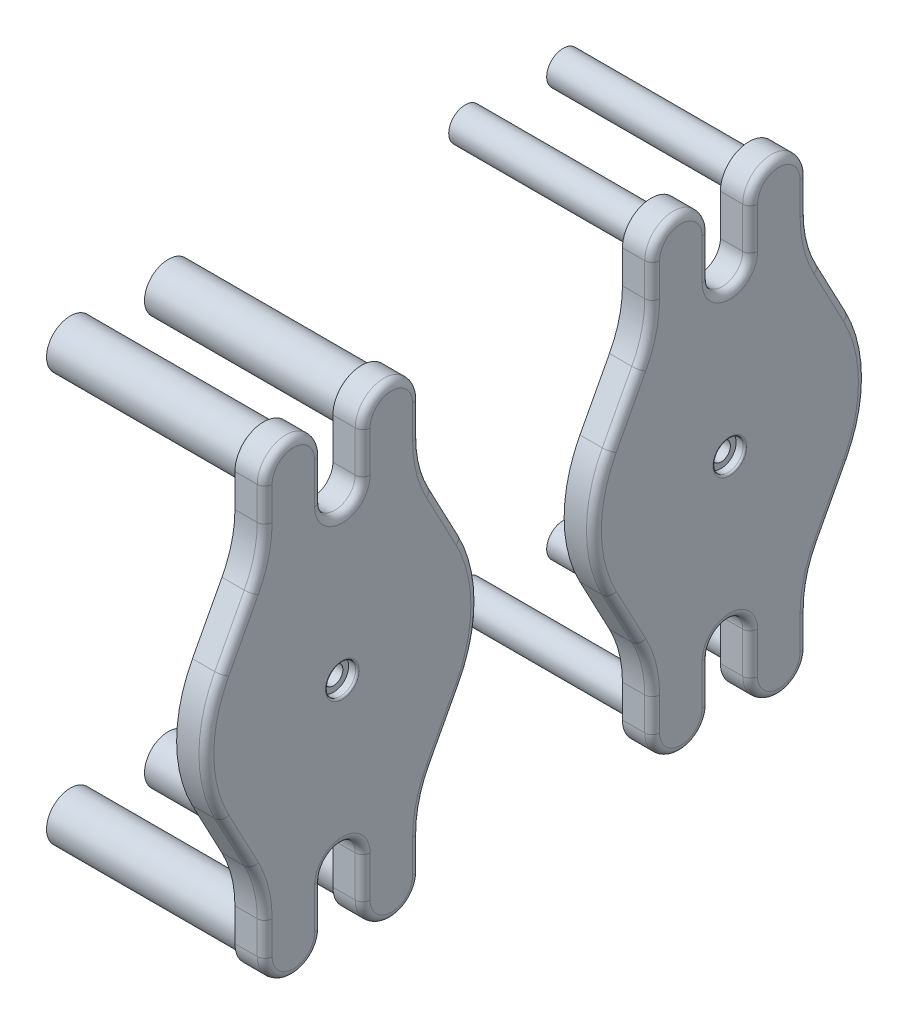
SolidWorks part; units mm, degrees
note: The reader was unsure of these and kept them because the rebuilt part matched: shared geometry of "Sketch12<6>", "Sketch13<3>".
other "Markup1"
sketch "Sketch9" plane through (-25.745, 62.7203, -36.576) normal (-0.5706, 0.1284, -0.8112) x (-0.8147, 0.0363, 0.5788)
ref_plane "Front Plane" through (0, 0, 0) normal (0, 0, 1) x (1, 0, 0)
ref_plane "Top Plane" through (0, 0, 0) normal (0, 1, 0) x (1, 0, 0)
ref_plane "Right Plane" through (0, 0, 0) normal (1, 0, 0) x (0, 0, -1)
sketch "Sketch1" plane through (0, 0, 0) normal (0, 0, 1) x (1, 0, 0)
  line L0 (8.255, 0) -> (-8.255, 0) construction
  line L1 (20.255, 0) -> (-20.255, 0) construction
  line L2 (8.255, 0) -> (8.255, 18.25)
  line L3 (8.255, 18.25) -> (20.255, 18.25)
  line L4 (20.255, 18.25) -> (20.255, 0)
  line L5 (8.255, 0) -> (20.255, 0)
  point P4 (0, 0)
  point P8 (0, 0)
  dimension "D1" = 16.51
  dimension "D2" = 12
  dimension "D3" = 18.25
revolve "Revolve1" add sketch "Sketch1" angle 360 about L5
sketch "Sketch2" plane through (8.255, 0, 0) normal (-1, 0, 0) x (0, 0, 1)
  circle A0 centre (0, 0) radius 3.7145
  dimension "D1" = 7.429
extrude "Cut-Extrude1" cut sketch "Sketch2" against normal blind 8.5725
sketch "Sketch3" plane through (20.255, 0, 0) normal (1, 0, 0) x (0, 0, -1)
  line L0 (-20.8953, -55) -> (-20.8953, -46.1532)
  line L1 (13.175, -55) -> (-13.175, -55) construction
  line L2 (13.175, -55) -> (13.175, 55) construction
  line L3 (13.175, 55) -> (-13.175, 55) construction
  line L4 (-13.175, -55) -> (-13.175, 55) construction
  line L5 (13.175, -55) -> (-13.175, 55) construction
  line L6 (13.175, 55) -> (-13.175, -55) construction
  line L7 (-24.3823, -32.1152) -> (-32.3245, -17.1152)
  line L9 (-5.4548, -55) -> (-5.4548, -44)
  line L11 (5.4547, -44) -> (5.4547, -55)
  line L12 (20.8953, -55) -> (20.8953, -46.1532)
  line L13 (24.3823, -32.1152) -> (32.3245, -17.1152)
  line L14 (55, 0) -> (-55, 0) construction
  line L15 (13.175, -55) -> (-13.175, 55) construction
  line L16 (13.175, 55) -> (-13.175, -55) construction
  line L17 (13.175, 55) -> (-13.175, 55) construction
  line L18 (24.3823, 32.1152) -> (32.3245, 17.1152)
  line L19 (20.8953, 55) -> (20.8953, 46.1532)
  line L20 (5.4547, 44) -> (5.4547, 55)
  line L21 (-5.4548, 55) -> (-5.4548, 44)
  line L22 (-24.3823, 32.1152) -> (-32.3245, 17.1152)
  line L23 (-20.8953, 55) -> (-20.8953, 46.1532)
  arc A15 (32.3245, -17.1152) -> (32.3245, 17.1152) centre (0, 0) ccw
  arc A16 (-5.4548, 55) -> (-20.8953, 55) centre (-13.175, 55) ccw
  arc A17 (-20.8953, -55) -> (-5.4548, -55) centre (-13.175, -55) ccw
  arc A18 (5.4547, -55) -> (20.8953, -55) centre (13.175, -55) ccw
  arc A19 (20.8953, 55) -> (5.4547, 55) centre (13.175, 55) ccw
  arc A20 (-5.4548, -44) -> (5.4547, -44) centre (0, -44) cw
  arc A21 (20.8953, -46.1532) -> (24.3823, -32.1152) centre (50.8953, -46.1532) cw
  arc A22 (-20.8953, -46.1532) -> (-24.3823, -32.1152) centre (-50.8953, -46.1532) ccw
  arc A23 (-20.8953, 46.1532) -> (-24.3823, 32.1152) centre (-50.8953, 46.1532) cw
  arc A24 (20.8953, 46.1532) -> (24.3823, 32.1152) centre (50.8953, 46.1532) ccw
  arc A25 (-5.4548, 44) -> (5.4547, 44) centre (0, 44) ccw
  arc A26 (5.4547, 55) -> (20.8953, 55) centre (13.175, 55) cw
  arc A27 (-20.8953, 55) -> (-5.4548, 55) centre (-13.175, 55) cw
  arc A29 (-32.3245, 17.1152) -> (-32.3245, -17.1152) centre (0, 0) ccw
  circle M2 centre (0, 0) radius 18.25
  dimension "D3" = 15.4405
  dimension "D5" = 7.7203
  dimension "D4" = 30
  dimension "D7" = 15
  dimension "D9" = 110
  dimension "D1" = 73.152
  dimension "D6" = 15
  dimension "D2" = 26.35
  dimension "D8" = 11
extrude "Boss-Extrude1" add sketch "Sketch3" along normal blind 8 separate body contours L22 A29 L7 A22 L0 A17 L9 A20 L11 A18 L12 A21 L13 A15 L18 A24 L19 A19 L20 A25 L21 A16 L23 A23 M2 | M2
sketch "Sketch4" plane through (20.255, 0, 0) normal (-1, 0, 0) x (0, 0, 1)
  line L0 (-20.8953, 55) -> (-5.4547, 55) construction
  line L1 (13.175, -55) -> (-13.175, -55) construction
  line L2 (13.175, -55) -> (13.175, 55) construction
  line L3 (13.175, 55) -> (-13.175, 55) construction
  line L4 (-13.175, -55) -> (-13.175, 55) construction
  line L5 (13.175, -55) -> (-13.175, 55) construction
  line L6 (13.175, 55) -> (-13.175, -55) construction
  circle A0 centre (-13.175, 55) radius 4.75
  circle A1 centre (13.175, -55) radius 4.75
  circle A2 centre (13.175, 55) radius 4.75
  circle A3 centre (-13.175, -55) radius 4.75
  arc A4 (-5.4547, 55) -> (-20.8953, 55) centre (-13.175, 55) ccw construction
  circle A5 centre (-13.175, 55) radius 6.4
  circle A6 centre (13.175, 55) radius 6.4
  circle A7 centre (13.175, -55) radius 6.4
  circle A8 centre (-13.175, -55) radius 6.4
  point P6 (0, 0)
  dimension "D1" = 9.5
  dimension "D2" = 12.8
extrude "Boss-Extrude2" add sketch "Sketch4" along normal blind 52
sketch "Sketch5" plane through (8.255, 0, 0) normal (-1, 0, 0) x (0, 0, 1)
  circle A0 centre (0, 0) radius 18.25
  dimension "D1" = 36.5
fillet "Fillet1" radius 2 24 edges at (28.255, 38.9209, 21.7801) (28.255, 50.5766, 20.8953) (28.255, 62.7203, 13.175) (28.255, 49.5, 5.4548) (28.255, 38.5453, 0) (28.255, 49.5, -5.4547) (28.255, 62.7203, -13.175) (28.255, 50.5766, -20.8953) (28.255, 38.9209, -21.7801) (28.255, 24.6152, -28.3534) (28.255, 0, -36.576) (28.255, -24.6152, -28.3534) (28.255, -38.9209, -21.7801) (28.255, -50.5766, -20.8953) (28.255, -62.7202, -13.175) (28.255, -49.5, -5.4547) (28.255, -38.5452, 0) (28.255, -49.5, 5.4548) (28.255, -62.7202, 13.175) (28.255, -50.5766, 20.8953) (28.255, -38.9209, 21.7801) (28.255, -24.6152, 28.3534) (28.255, 0, 36.576) (28.255, 24.6152, 28.3534)
sketch "Sketch6" plane through (8.255, 0, 0) normal (-1, 0, 0) x (0, 0, 1)
  circle A2 centre (0, 0) radius 13.15
  dimension "D1" = 26.3
extrude "Cut-Extrude2" cut sketch "Sketch6" against normal blind 12
ref_plane "Plane1" through (0, 0, 38) normal (0, 0, 1) x (1, 0, 0)
ref_plane "Plane2" through (19.255, 0, 0) normal (-1, 0, 0) x (0, 0, 1)
sketch "Sketch10" plane through (19.255, 0, 0) normal (-1, 0, 0) x (0, 0, 1)
  line L1 (37.5, -101.6) -> (-37.5, -101.6)
  line L2 (37.5, -101.6) -> (37.5, 101.6)
  line L3 (37.5, 101.6) -> (-37.5, 101.6)
  line L4 (-37.5, -101.6) -> (-37.5, 101.6)
  line L5 (37.5, -101.6) -> (-37.5, 101.6) construction
  line L6 (37.5, 101.6) -> (-37.5, -101.6) construction
  circle A0 centre (-13.175, 55) radius 7.15
  circle A1 centre (13.175, 55) radius 7.15
  circle A2 centre (-13.175, -55) radius 7.15
  circle A3 centre (13.175, -55) radius 7.15
  circle A4 centre (-13.175, 55) radius 6.4 construction
  circle A5 centre (0, 0) radius 18.75
  circle A7 centre (0, 0) radius 18.25 construction
  point P0 (0, 0)
  dimension "D3" = 0.75
  dimension "D4" = 0.5
  dimension "D1" = 75
  dimension "D2" = 203.2
extrude "Boss-Extrude3" [suppressed] add sketch "Sketch10" along normal blind 63.5 separate body
sketch "Sketch11" [suppressed] plane through (0, -101.6, 0) normal (0, -1, 0) x (1, 0, 0)
  line L0 (-38.245, -37.5) -> (-38.245, 37.5) construction
  line L1 (8.505, -27.5) -> (-21.495, -27.5) construction
  line L2 (8.505, -27.5) -> (8.505, 27.5) construction
  line L3 (8.505, 27.5) -> (-21.495, 27.5) construction
  line L4 (-21.495, -27.5) -> (-21.495, 27.5) construction
  line L5 (8.505, -27.5) -> (-21.495, 27.5) construction
  line L6 (8.505, 27.5) -> (-21.495, -27.5) construction
  line L7 (-38.245, 37.5) -> (25.255, 37.5) construction
  circle A0 centre (-21.495, 27.5) radius 2.25
  circle A1 centre (8.505, 27.5) radius 2.25
  circle A2 centre (-21.495, -27.5) radius 2.25
  circle A3 centre (8.505, -27.5) radius 2.25
  circle A4 centre (-6.495, 0) radius 17.5
  dimension "D3" = 4.5
  dimension "D4" = 35
  dimension "D1" = 30
  dimension "D2" = 55
  dimension "D5" = 31.75
  dimension "D6" = 37.5
extrude "Cut-Extrude5" [suppressed] cut sketch "Sketch11" against normal blind 6 contours A0 | A1 | A2 | A3
sketch "Sketch12" plane through (28.255, 0, 0) normal (1, 0, 0) x (0, 0, -1)
  circle A0 centre (0, 0) radius 4.05
  circle A1 centre (0, 0) radius 2.5
  dimension "D1" = 8.1
  dimension "D2" = 5
extrude "Cut-Extrude6" cut sketch "Sketch12" against normal blind 2.36 contours A0
extrude "Cut-Extrude7" cut sketch "Sketch12<6>" against normal up to surface (8 mm away) contours A1 up to face at (20.255, -48.6, -13.175)
sketch "Sketch12<6>" plane through (28.255, 0, 0) normal (1, 0, 0) x (0, 0, -1) same geometry as "Sketch12"
fillet "Fillet2" radius 0.5 1 edges at (28.255, 4.05, 0)
combine bodies "Combine1" operation type add bodies to combine 124 127
fillet "Fillet3" radius 1 5 edges at (20.255, 18.25, 0) (20.255, -48.6, 13.175) (20.255, -48.6, -13.175) (20.255, 61.4, 13.175) (20.255, 61.4, -13.175)
move or copy body "Body-Move/Copy1" bodies to move or copy 128 copy yes number of copies 1 translate (0, 0, -104.2302)
sketch "Sketch13" plane through (-31.745, 0, 0) normal (-1, 0, 0) x (0, 0, 1)
  circle A0 centre (-91.0552, -55) radius 4.45
  circle A1 centre (-117.4052, -55) radius 4.45
  circle A2 centre (-117.4052, 55) radius 4.45
  circle A3 centre (-91.0552, 55) radius 4.45
  circle A5 centre (-117.4052, -55) radius 4.75 construction
  circle A6 centre (-117.4052, 55) radius 7.4 construction
  circle A7 centre (-117.4052, 55) radius 7.4
  circle A8 centre (-91.0552, 55) radius 7.4 construction
  circle A9 centre (-91.0552, 55) radius 7.4
  circle A10 centre (-117.4052, -55) radius 7.4 construction
  circle A11 centre (-117.4052, -55) radius 7.4
  circle A12 centre (-91.0552, -55) radius 7.4 construction
  circle A13 centre (-91.0552, -55) radius 7.4
  dimension "D1" = 0.3
extrude "Cut-Extrude8" cut sketch "Sketch13" against normal up to surface (52 mm away)
extrude "Boss-Extrude4" add sketch "Sketch13<3>" against normal up to surface (50 mm away) from offset 2 contours A3 | A1 | A0 | A2 offset against normal yes
sketch "Sketch13<3>" plane through (-31.745, 0, 0) normal (-1, 0, 0) x (0, 0, 1) same geometry as "Sketch13"
fillet "Fillet4" radius 1 4 edges at (20.255, 59.45, -91.0552) (20.255, -50.55, -117.4052) (20.255, -50.55, -91.0552) (20.255, 59.45, -117.4052)
